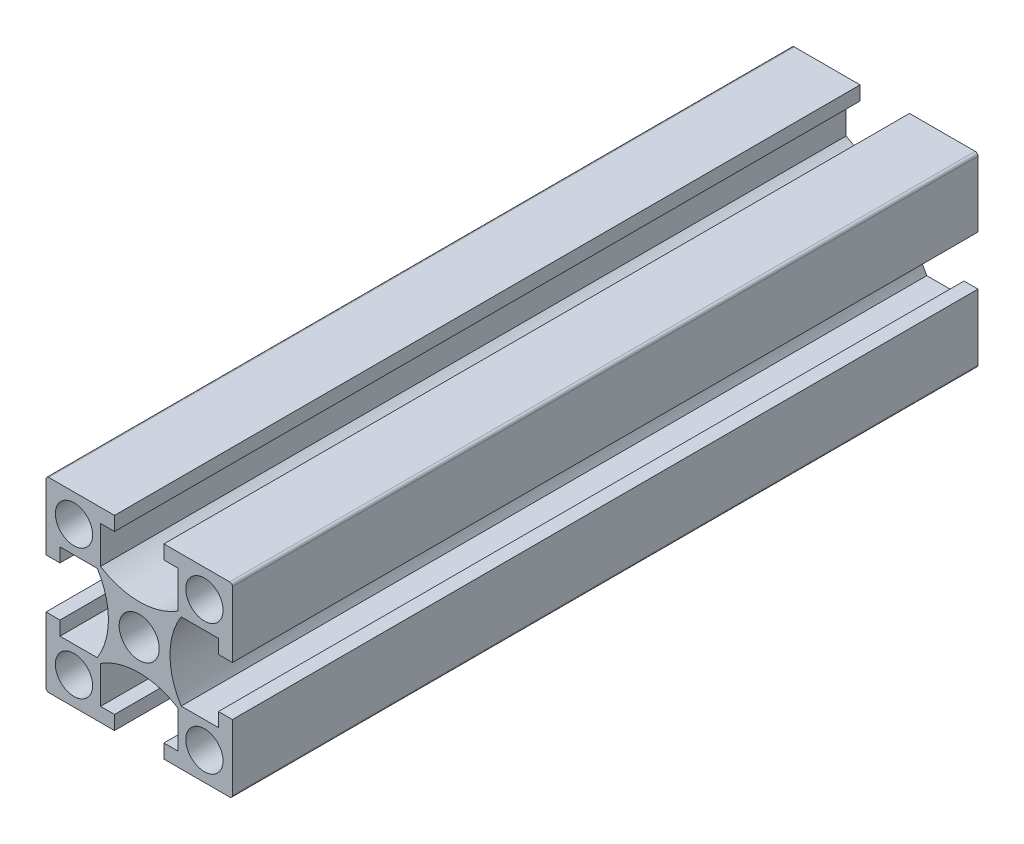
SolidWorks part; units mm, degrees
ref_plane "정면" through (0, 0, 0) normal (0, 0, 1) x (1, 0, 0)
ref_plane "윗면" through (0, 0, 0) normal (0, 1, 0) x (1, 0, 0)
ref_plane "우측면" through (0, 0, 0) normal (1, 0, 0) x (0, 0, -1)
sketch "스케치1" plane through (0, 0, 0) normal (0, 0, 1) x (1, 0, 0)
  line L0 (0, 32.0265) -> (0, -31.6588) construction
  line L1 (-10, 10) -> (-10, -10)
  line L2 (-10, 10) -> (10, 10)
  line L3 (-10, 2.65) -> (-8.5, 2.65)
  line L4 (13.6618, 0) -> (-11.6993, 0) construction
  line L5 (-8.5, 2.65) -> (-8.5, 4.15)
  line L6 (-8.5, 4.15) -> (-4.5032, 4.15)
  line L7 (-10, -2.65) -> (-8.5, -2.65)
  line L8 (-8.5, -2.65) -> (-8.5, -4.15)
  line L9 (-8.5, -4.15) -> (-4.5032, -4.15)
  line L10 (-10, -10) -> (10, -10)
  line L11 (10, 10) -> (10, -10)
  circle A0 centre (-7, 7) radius 2
  circle A1 centre (-7, -7) radius 2
  arc A2 (-4.5032, 4.15) -> (-4.5032, -4.15) centre (-11.0587, 0) cw
  circle A3 centre (0, 0) radius 2.15
  circle A4 centre (7, 7) radius 2
  circle A5 centre (7, -7) radius 2
  point P21 (-10, 0)
  point P23 (-3.3, 0)
  point P31 (0, -10)
  point P32 (0, 10)
  dimension "D3" = 4
  dimension "D9" = 6.7
  dimension "D10" = 4.3
  dimension "D11" = 7.7587
  dimension "D1" = 20
  dimension "D2" = 20
  dimension "D4" = 14
  dimension "D5" = 14
  dimension "D6" = 5.3
  dimension "D7" = 8.3
  dimension "D8" = 1.5
extrude "보스-돌출1" add sketch "스케치1" along normal blind 80 contours A0 | A4 | A3 | A5 | A1 | A2 L6 L5 L3 L1 L7 L8 L9 | L2 L11 L10 L1 region at (-6.6069, 0, 0) region at (-7, 7, 0) region at (-7, -7, 0) region at (0, 0, 0) region at (7, 7, 0) region at (7, -7, 0)
extrude "컷-돌출1" cut sketch "스케치1<3>" along normal up to next contours A2 L6 L5 L3 L1 L7 L8 L9 region at (-6.6069, 0, 0)
sketch "스케치1<3>" plane through (0, 0, 0) normal (0, 0, 1) x (1, 0, 0) same geometry as "스케치1"
pattern_circular "원형 패턴1" count 4 over 360 about axis through (0, 0, 80) along (0, 0, -1) of "컷-돌출1" reverse direction yes
fillet "필렛1" radius 0.3 4 edges at (10, -10, 40) (-10, -10, 40) (-10, 10, 40) (10, 10, 40)
sketch "스케치3" plane through (0, -10, 0) normal (0, -1, 0) x (1, 0, 0)
  line L0 (4.15, 80) -> (-4.15, 80) construction
  circle A0 centre (0, 69) radius 2.5
  circle A1 centre (0, 11) radius 2.5
  dimension "D1" = 11
  dimension "D2" = 11
extrude "컷-돌출2" cut sketch "스케치3" against normal through all
